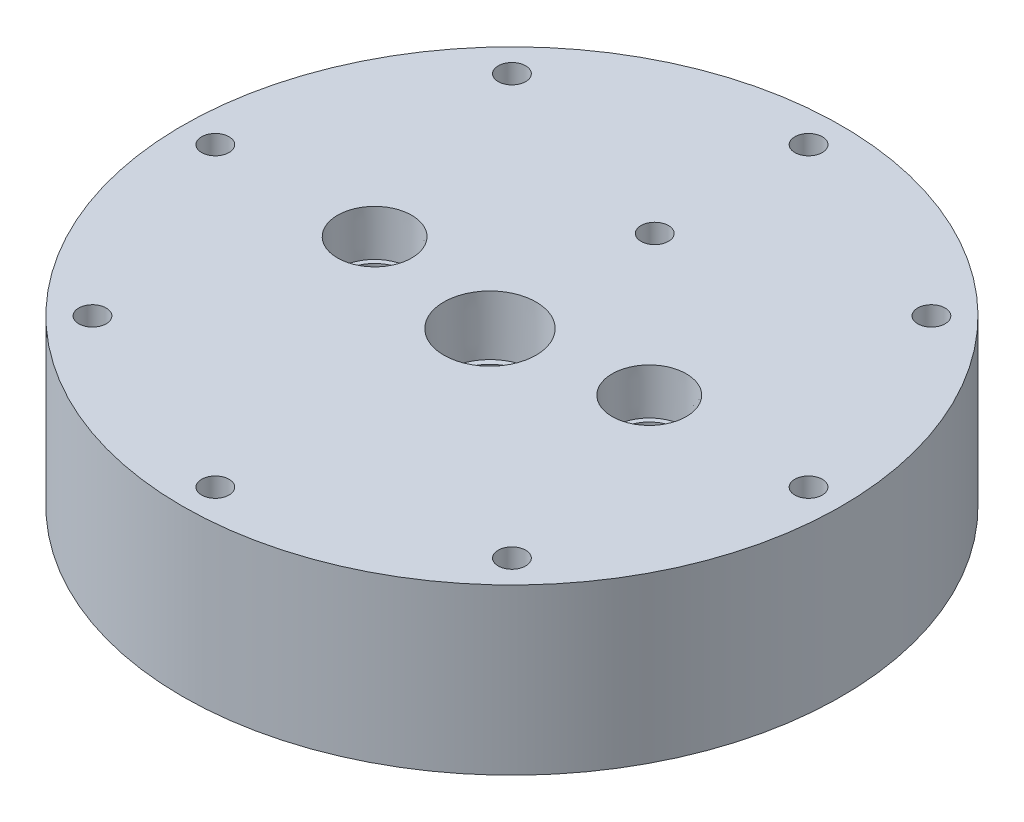
SolidWorks part; units mm, degrees
ref_plane "Front Plane" through (0, 0, 0) normal (0, 0, 1) x (1, 0, 0)
ref_plane "Top Plane" through (0, 0, 0) normal (0, 1, 0) x (1, 0, 0)
ref_plane "Right Plane" through (0, 0, 0) normal (1, 0, 0) x (0, 0, -1)
ref_axis "Axial" through (0, 53.34, 0) along (0, -1, 0)
ref_plane "Bottom Plane" through (0, -50.8, 0) normal (0, 1, 0) x (1, 0, 0)
sketch "Sketch1" plane through (0, 0, 0) normal (0, 1, 0) x (1, 0, 0)
  circle A0 centre (0, 0) radius 76.2
  dimension "D1" = 152.4
extrude "Billet" add sketch "Sketch1" against normal blind 50.8
sketch "Sketch3" plane through (0, -50.8, 0) normal (0, 1, 0) x (1, 0, 0)
  circle A0 centre (0, 0) radius 19.05
  dimension "D1" = 38.1
extrude "Lox Plate" cut sketch "Sketch3" along normal blind 13.97
sketch "Sketch5" plane through (0, -50.8, 0) normal (0, 1, 0) x (1, 0, 0)
  circle A0 centre (0, 0) radius 13.97
  dimension "D1" = 27.94
extrude "Lox Dome" cut sketch "Sketch5" along normal blind 20.32
sketch "Sketch7" plane through (0, 0, 0) normal (0, 1, 0) x (1, 0, 0)
  circle A1 centre (0, 0) radius 76.2
  dimension "D2" = 152.4
extrude "Top Mill" cut sketch "Sketch7" against normal blind 12.7
sketch "Sketch11" plane through (0, -50.8, 0) normal (0, 1, 0) x (1, 0, 0)
  line L0 (0, 82.3071) -> (0, -82.946) construction
  circle A0 centre (0, 68.58) radius 3.175
  dimension "D1" = 6.35
  dimension "D2" = 68.58
extrude "1/4\" Bolt Hole" cut sketch "Sketch11" along normal up to next
pattern_circular "Bolt Pattern" count 8 over 360 about axis through (0, 53.34, 0) along (0, -1, 0) of "1/4\" Bolt Hole"
sketch "Sketch12" plane through (0, -50.8, 0) normal (0, 1, 0) x (1, 0, 0)
  circle A0 centre (0, 0) radius 60.96
  dimension "D1" = 121.92
extrude "Kerosene Plate" cut sketch "Sketch12" along normal blind 10.16
hole_wizard "Lox Inlet-1/2 NPT Tapped Hole3" positions "Sketch20" profile "Sketch21" size "1/2" standard "ANSI Inch" end condition through all
sketch "Sketch20" plane through (0, -12.7, 0) normal (0, 1, 0) x (1, 0, 0)
  line L0 (0, 40.1697) -> (0, -38.6779) construction
  point P8 (0, -5.08)
  dimension "D1" = 5.08
sketch "Sketch21" plane through (0, -12.7, 5.08) normal (1, 0, 0) x (0, 0, 1)
  line L0 (0, 0) -> (0, 38.1)
  line L1 (0, 38.1) -> (8.9281, 38.1)
  line L2 (-10.2617, 13.462) -> (-10.6647, 0) construction
  line L3 (8.9281, 38.1) -> (8.9281, 13.462)
  line L4 (8.9281, 13.462) -> (10.2617, 13.462)
  line L5 (10.2617, 13.462) -> (10.6647, 0)
  line L7 (10.6647, 0) -> (0, 0)
  line L8 (0, -6.35) -> (0, 107.95) construction
  line L11 (-8.9281, 13.462) -> (-10.2617, 13.462) construction
  dimension "Thru Tap Drill Dia." = 17.8562
  dimension "Thru Tap Drill Depth" = 38.1
  dimension "Thread Dia." = 21.3295
  dimension "Thread Angle" = 3.43
  dimension "Thread Depth" = 13.462
hole_wizard "Kerosene Inlet-3/8 NPT Tapped Hole1" positions "Sketch24" profile "Sketch25" size "3/8" standard "ANSI Inch" end condition through all
sketch "Sketch24" plane through (0, -12.7, 0) normal (0, 1, 0) x (1, 0, 0)
  point P0 (-31.75, 0)
  point P2 (31.75, 0)
  dimension "D1" = 31.75
  dimension "D2" = 31.75
sketch "Sketch25" plane through (-31.75, -12.7, 0) normal (1, 0, 0) x (0, 0, 1)
  line L0 (0, 0) -> (0, 38.1)
  line L1 (0, 38.1) -> (7.1374, 38.1)
  line L2 (-8.2632, 10.414) -> (-8.575, 0) construction
  line L3 (7.1374, 38.1) -> (7.1374, 10.414)
  line L4 (7.1374, 10.414) -> (8.2632, 10.414)
  line L5 (8.2632, 10.414) -> (8.575, 0)
  line L7 (8.575, 0) -> (0, 0)
  line L8 (0, -6.35) -> (0, 107.95) construction
  line L11 (-7.1374, 10.414) -> (-8.2632, 10.414) construction
  dimension "Thru Tap Drill Dia." = 14.2748
  dimension "Thru Tap Drill Depth" = 38.1
  dimension "Thread Dia." = 17.15
  dimension "Thread Angle" = 3.43
  dimension "Thread Depth" = 10.414
sketch "Sketch14" plane through (0, 0, 0) normal (0, 1, 0) x (1, 0, 0)
  line L0 (0, 82.1507) -> (0, -86.6258) construction
  circle A0 centre (0, 33.02) radius 3.175
  dimension "D1" = 6.35
  dimension "D2" = 33.02
extrude "Manifold hole" cut sketch "Sketch14" against normal up to next
sketch "Sketch15" plane through (0, -40.64, 0) normal (0, 1, 0) x (1, 0, 0)
  line L0 (0, 72.5611) -> (0, -49.1199) construction
  circle A0 centre (0, 33.02) radius 7.62
  circle A1 centre (0, 33.02) radius 8.89
  dimension "D1" = 15.24
  dimension "D2" = 17.78
extrude "Manifold seal" cut sketch "Sketch15" along normal blind 1.27
sketch "Sketch26" plane through (0, -36.83, 0) normal (0, -1, 0) x (1, 0, 0)
  circle A0 centre (0, 0) radius 16.51
  circle A1 centre (0, 0) radius 17.78
  dimension "D1" = 35.56
  dimension "D2" = 33.02
extrude "Lox Plate O Ring" cut sketch "Sketch26" against normal blind 1.27
